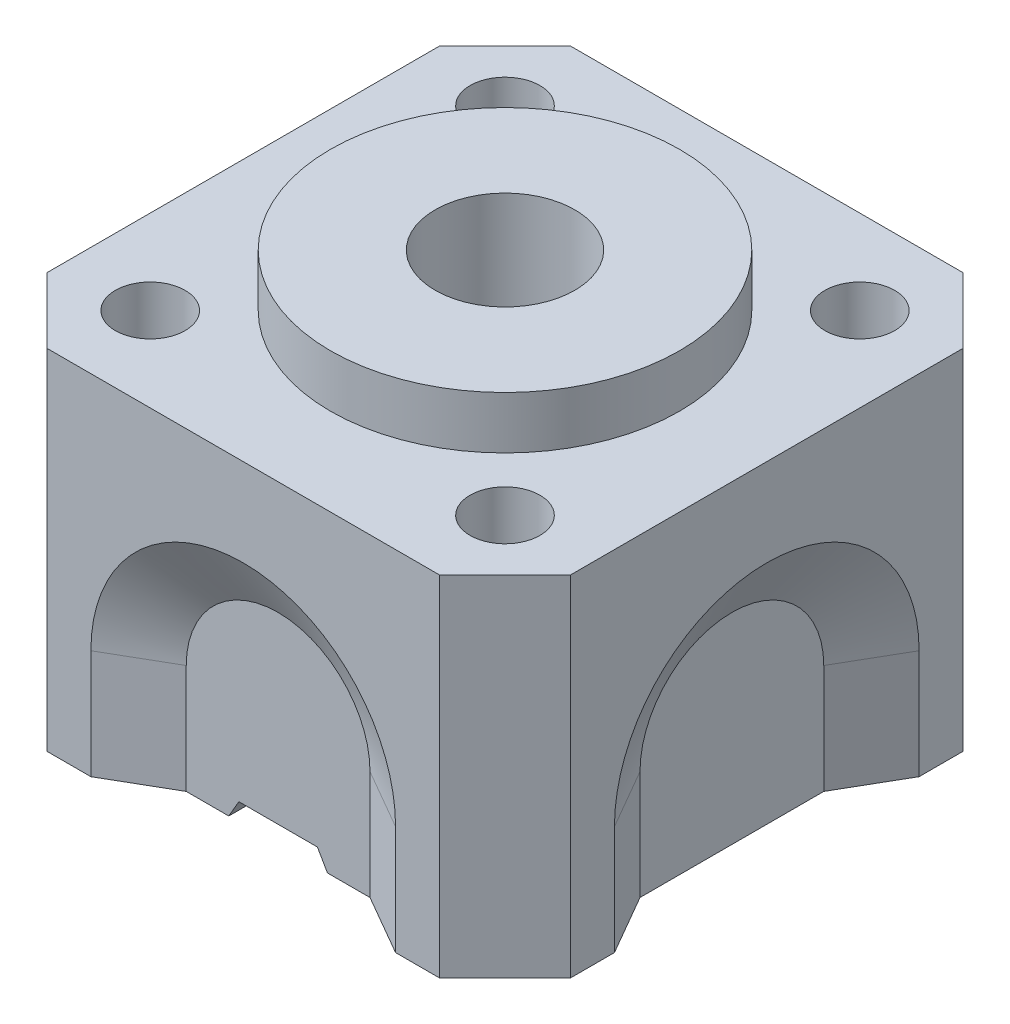
SolidWorks part; units mm, degrees
ref_plane "Front Plane" through (0, 0, 0) normal (0, 0, 1) x (1, 0, 0)
ref_plane "Top Plane" through (0, 0, 0) normal (0, 1, 0) x (1, 0, 0)
ref_plane "Right Plane" through (0, 0, 0) normal (1, 0, 0) x (0, 0, -1)
sketch "Sketch1" plane through (0, 0, 0) normal (0, 1, 0) x (1, 0, 0)
  line L1 (-60, -60) -> (60, -60)
  line L2 (-60, -60) -> (-60, 60)
  line L3 (-60, 60) -> (60, 60)
  line L4 (60, -60) -> (60, 60)
  line L5 (-60, -60) -> (60, 60) construction
  line L6 (-60, 60) -> (60, -60) construction
  point P0 (0, 0)
  dimension "D1" = 120
  dimension "D2" = 120
extrude "Boss-Extrude1" add sketch "Sketch1" along normal blind 80
chamfer "Chamfer1" distance 15 4 edges at (60, 40, -60) (-60, 40, -60) (-60, 40, 60) (60, 40, 60)
sketch "Sketch2" plane through (0, 80, 0) normal (0, 1, 0) x (1, 0, 0)
  line L0 (-60, 0) -> (60, 0) construction
  line L1 (0, 60) -> (0, -60) construction
  line L2 (0, 0) -> (-52.5, 52.5) construction
  line L3 (0, 0) -> (52.5, 52.5) construction
  line L4 (0, 0) -> (52.5, -52.5) construction
  line L5 (0, 0) -> (-52.5, -52.5) construction
  line L8 (60, -45) -> (60, 45)
  line L9 (60, 45) -> (45, 60)
  line L10 (45, 60) -> (-45, 60)
  line L11 (-45, 60) -> (-60, 45)
  line L12 (-60, 45) -> (-60, -45)
  line L13 (-60, -45) -> (-45, -60)
  line L14 (-45, -60) -> (45, -60)
  line L15 (45, -60) -> (60, -45)
  line L16 (60, -45) -> (60, 45)
  line L17 (60, 45) -> (45, 60)
  line L18 (45, 60) -> (-45, 60)
  line L19 (-45, 60) -> (-60, 45)
  line L20 (-60, 45) -> (-60, -45)
  line L21 (-60, -45) -> (-45, -60)
  line L22 (-45, -60) -> (45, -60)
  line L23 (45, -60) -> (60, -45)
  circle A1 centre (-40.6586, 40.6586) radius 8
  circle A2 centre (0, 0) radius 57.5 construction
  circle A3 centre (40.6586, 40.6586) radius 8
  circle A4 centre (40.6586, -40.6586) radius 8
  circle A5 centre (-40.6586, -40.6586) radius 8
  circle A6 centre (0, 0) radius 16
  circle A7 centre (0, 0) radius 40
  point P30 (0, 0)
  dimension "D2" = 57.5
  dimension "D3" = 16
  dimension "D5" = 32
  dimension "D6" = 80
  dimension "D4" = 4
  dimension "D1" = 0
extrude "Cut-Extrude1" cut sketch "Sketch2" against normal blind 80 contours A4 | A6 | A3 | A1 | A5
sketch "Sketch3" plane through (60, 0, 0) normal (1, 0, 0) x (0, 0, -1)
  line L0 (-21.0615, 0) -> (-21.0615, 25)
  line L1 (21.0615, 25) -> (21.0615, 0)
  line L2 (0, 80) -> (0, 0) construction
  line L4 (-45, 0) -> (45, 0)
  line L5 (45, 0) -> (45, 80)
  line L6 (45, 80) -> (-45, 80)
  line L7 (-45, 80) -> (-45, 0)
  line L8 (-45, 0) -> (45, 0)
  line L9 (45, 0) -> (45, 80)
  line L10 (45, 80) -> (-45, 80)
  line L11 (-45, 80) -> (-45, 0)
  arc A0 (-21.0615, 25) -> (21.0615, 25) centre (0, 25) cw
  line M6 (-45, 0) -> (45, 0)
  dimension "D2" = 21.0615
  dimension "D3" = 25
  dimension "D1" = 0
extrude "Cut-Extrude2" cut sketch "Sketch3" against normal blind 8 contours L2 A0 L0 M6 | A0 L2 L8 L1 region at (60, 21.0368, 9.8968) region at (60, 21.0368, -9.8968)
chamfer "Chamfer3" distance 8 angle 60 3 edges at (60, 12.5, 21.0615) (60, 46.0615, 0) (60, 12.5, -21.0615) first distance on face at (56, 12.5, 21.0615) first distance on face at (56, 35.5307, 0) first distance on face at (56, 12.5, -21.0615)
pattern_circular "CirPattern2" count 4 over 360 about axis through (0, 0, 0) along (0, 1, 0) of "Cut-Extrude2", "Chamfer3"
sketch "Sketch5" plane through (0, 80, 0) normal (0, 1, 0) x (1, 0, 0)
  line L8 (60, -45) -> (60, 45)
  line L9 (60, 45) -> (45, 60)
  line L10 (45, 60) -> (-45, 60)
  line L11 (-45, 60) -> (-60, 45)
  line L12 (-60, 45) -> (-60, -45)
  line L13 (-60, -45) -> (-45, -60)
  line L14 (-45, -60) -> (45, -60)
  line L15 (45, -60) -> (60, -45)
  line L16 (60, -45) -> (60, 45)
  line L17 (60, 45) -> (45, 60)
  line L18 (45, 60) -> (-45, 60)
  line L19 (-45, 60) -> (-60, 45)
  line L20 (-60, 45) -> (-60, -45)
  line L21 (-60, -45) -> (-45, -60)
  line L22 (-45, -60) -> (45, -60)
  line L23 (45, -60) -> (60, -45)
  circle A0 centre (0, 0) radius 40
  circle A1 centre (0, 0) radius 16 construction
  circle A2 centre (0, 0) radius 16
  circle M14 centre (0, 0) radius 16
  dimension "D2" = 80
  dimension "D1" = 0
extrude "Boss-Extrude2" add sketch "Sketch5" along normal blind 12 contours A0 M14 region at (-38.8686, 80, 0)
sketch "Sketch6" plane through (0, 0, 0) normal (0, -1, 0) x (1, 0, 0)
  line L24 (-45, -60) -> (-34.9179, -60)
  line L25 (-34.9179, -60) -> (-21.0615, -52)
  line L26 (-21.0615, -52) -> (21.0615, -52)
  line L27 (21.0615, -52) -> (34.9179, -60)
  line L28 (34.9179, -60) -> (45, -60)
  line L29 (45, -60) -> (60, -45)
  line L30 (60, -45) -> (60, -34.9179)
  line L31 (60, -34.9179) -> (52, -21.0615)
  line L32 (52, -21.0615) -> (52, 21.0615)
  line L33 (52, 21.0615) -> (60, 34.9179)
  line L34 (60, 34.9179) -> (60, 45)
  line L35 (60, 45) -> (45, 60)
  line L36 (45, 60) -> (34.9179, 60)
  line L37 (34.9179, 60) -> (21.0615, 52)
  line L38 (21.0615, 52) -> (-21.0615, 52)
  line L39 (-21.0615, 52) -> (-34.9179, 60)
  line L40 (-34.9179, 60) -> (-45, 60)
  line L41 (-45, 60) -> (-60, 45)
  line L42 (-60, 45) -> (-60, 34.9179)
  line L43 (-60, 34.9179) -> (-52, 21.0615)
  line L44 (-52, 21.0615) -> (-52, -21.0615)
  line L45 (-52, -21.0615) -> (-60, -34.9179)
  line L46 (-60, -34.9179) -> (-60, -45)
  line L47 (-60, -45) -> (-45, -60)
  line L48 (-45, -60) -> (-34.9179, -60)
  line L49 (-34.9179, -60) -> (-21.0615, -52)
  line L50 (-21.0615, -52) -> (21.0615, -52)
  line L51 (21.0615, -52) -> (34.9179, -60)
  line L52 (34.9179, -60) -> (45, -60)
  line L53 (45, -60) -> (60, -45)
  line L54 (60, -45) -> (60, -34.9179)
  line L55 (60, -34.9179) -> (52, -21.0615)
  line L56 (52, -21.0615) -> (52, 21.0615)
  line L57 (52, 21.0615) -> (60, 34.9179)
  line L58 (60, 34.9179) -> (60, 45)
  line L59 (60, 45) -> (45, 60)
  line L60 (45, 60) -> (34.9179, 60)
  line L61 (34.9179, 60) -> (21.0615, 52)
  line L62 (21.0615, 52) -> (-21.0615, 52)
  line L63 (-21.0615, 52) -> (-34.9179, 60)
  line L64 (-34.9179, 60) -> (-45, 60)
  line L65 (-45, 60) -> (-60, 45)
  line L66 (-60, 45) -> (-60, 34.9179)
  line L67 (-60, 34.9179) -> (-52, 21.0615)
  line L68 (-52, 21.0615) -> (-52, -21.0615)
  line L69 (-52, -21.0615) -> (-60, -34.9179)
  line L70 (-60, -34.9179) -> (-60, -45)
  line L71 (-60, -45) -> (-45, -60)
  circle A0 centre (0, 0) radius 32.5
  dimension "D2" = 65
  dimension "D1" = 0
extrude "Cut-Extrude3" cut sketch "Sketch6" against normal blind 25 contours A0
sketch "Sketch17" plane through (0, 0, 0) normal (0, -1, 0) x (1, 0, 0)
  line L24 (-45, -60) -> (-34.9179, -60)
  line L25 (-34.9179, -60) -> (-21.0615, -52)
  line L26 (-21.0615, -52) -> (21.0615, -52)
  line L27 (21.0615, -52) -> (34.9179, -60)
  line L28 (34.9179, -60) -> (45, -60)
  line L29 (45, -60) -> (60, -45)
  line L30 (60, -45) -> (60, -34.9179)
  line L31 (60, -34.9179) -> (52, -21.0615)
  line L32 (52, -21.0615) -> (52, 21.0615)
  line L33 (52, 21.0615) -> (60, 34.9179)
  line L34 (60, 34.9179) -> (60, 45)
  line L35 (60, 45) -> (45, 60)
  line L36 (45, 60) -> (34.9179, 60)
  line L37 (34.9179, 60) -> (21.0615, 52)
  line L38 (21.0615, 52) -> (-21.0615, 52)
  line L39 (-21.0615, 52) -> (-34.9179, 60)
  line L40 (-34.9179, 60) -> (-45, 60)
  line L41 (-45, 60) -> (-60, 45)
  line L42 (-60, 45) -> (-60, 34.9179)
  line L43 (-60, 34.9179) -> (-52, 21.0615)
  line L44 (-52, 21.0615) -> (-52, -21.0615)
  line L45 (-52, -21.0615) -> (-60, -34.9179)
  line L46 (-60, -34.9179) -> (-60, -45)
  line L47 (-60, -45) -> (-45, -60)
  line L48 (-45, -60) -> (-34.9179, -60)
  line L49 (-34.9179, -60) -> (-21.0615, -52)
  line L50 (-21.0615, -52) -> (21.0615, -52)
  line L51 (21.0615, -52) -> (34.9179, -60)
  line L52 (34.9179, -60) -> (45, -60)
  line L53 (45, -60) -> (60, -45)
  line L54 (60, -45) -> (60, -34.9179)
  line L55 (60, -34.9179) -> (52, -21.0615)
  line L56 (52, -21.0615) -> (52, 21.0615)
  line L57 (52, 21.0615) -> (60, 34.9179)
  line L58 (60, 34.9179) -> (60, 45)
  line L59 (60, 45) -> (45, 60)
  line L60 (45, 60) -> (34.9179, 60)
  line L61 (34.9179, 60) -> (21.0615, 52)
  line L62 (21.0615, 52) -> (-21.0615, 52)
  line L63 (-21.0615, 52) -> (-34.9179, 60)
  line L64 (-34.9179, 60) -> (-45, 60)
  line L65 (-45, 60) -> (-60, 45)
  line L66 (-60, 45) -> (-60, 34.9179)
  line L67 (-60, 34.9179) -> (-52, 21.0615)
  line L68 (-52, 21.0615) -> (-52, -21.0615)
  line L69 (-52, -21.0615) -> (-60, -34.9179)
  line L70 (-60, -34.9179) -> (-60, -45)
  line L71 (-60, -45) -> (-45, -60)
  circle A0 centre (0, 0) radius 32.5 construction
  circle A1 centre (0, 0) radius 32.5
  circle A2 centre (0, 0) radius 38.5
  circle M25 centre (0, 0) radius 32.5
  dimension "D2" = 6
  dimension "D1" = 0
extrude "Boss-Extrude3" add sketch "Sketch17" along normal blind 4 contours A2 M25 region at (-37.4111, 0, 0)
sketch "Sketch18" plane through (0, 0, 52) normal (0, 0, 1) x (1, 0, 0)
  line L0 (-9, 4) -> (9, 4)
  line L1 (-38.5, 0) -> (38.5, 0) construction
  line L2 (9, 4) -> (13.6188, -4)
  line L4 (-9, 4) -> (-13.6188, -4)
  line L5 (34.9179, 0) -> (21.0615, 0) construction
  line L6 (34.9179, 0) -> (45, 0) construction
  line L7 (34.9179, 0) -> (21.0615, 0)
  line L8 (34.9179, 0) -> (45, 0)
  line L9 (-38.5, 0) -> (-38.5, -4) construction
  line L10 (38.5, -4) -> (38.5, 0) construction
  line L11 (-38.5, -4) -> (38.5, -4) construction
  line L12 (-38.5, 0) -> (-38.5, -4)
  line L13 (38.5, -4) -> (38.5, 0)
  line L14 (-38.5, 0) -> (38.5, 0)
  line L15 (-38.5, -4) -> (38.5, -4)
  line L17 (0, 25) -> (0, -4) construction
  line L18 (0, 0) -> (0, 24.9121) construction
  line L19 (0, 25) -> (0, 92) construction
  line L20 (0, 4) -> (0, -4)
  line M13 (-21.0615, 0) -> (21.0615, 0)
  dimension "D1" = 18
  dimension "D2" = 30
  dimension "D3" = 8
extrude "Cut-Extrude4" cut sketch "Sketch18" against normal blind 156 contours L0 L20 L14 L2 | L20 L0 L4 M13 | L20 L4 L15 M13 | L14 L20 L15 L2 region at (-5.0992, 1.9242, 52) region at (5.0992, 1.9242, 52) region at (-6.2499, -2.0618, 52) region at (6.2499, -2.0618, 52)
